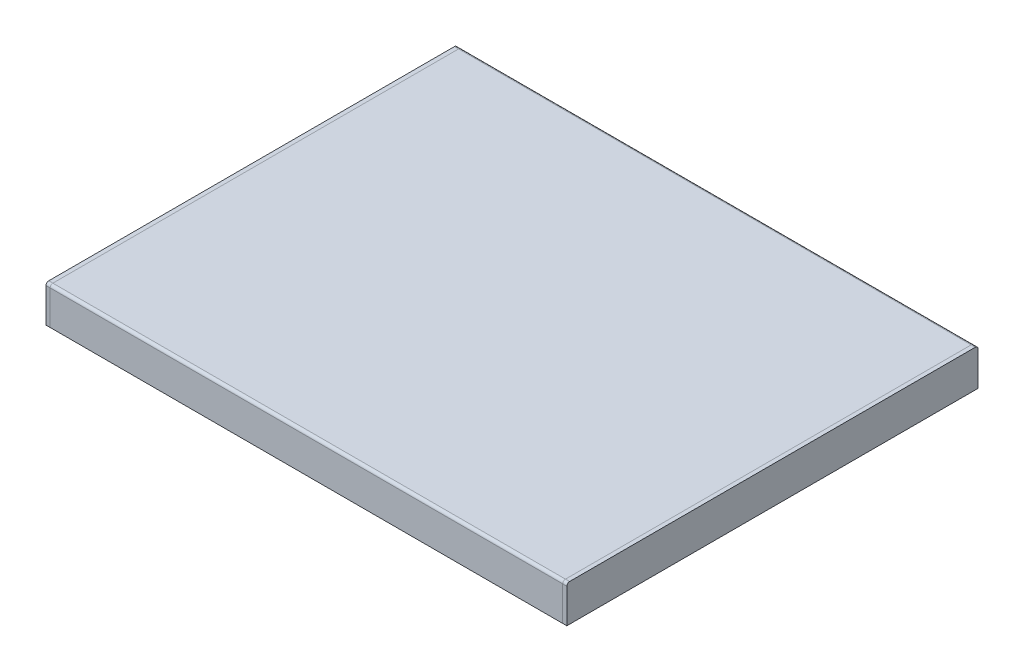
SolidWorks part; units mm, degrees
ref_plane "Front Plane" through (0, 0, 0) normal (0, 0, 1) x (1, 0, 0)
ref_plane "Top Plane" through (0, 0, 0) normal (0, 1, 0) x (1, 0, 0)
ref_plane "Right Plane" through (0, 0, 0) normal (1, 0, 0) x (0, 0, -1)
sketch "Sketch1" plane through (0, 0, 0) normal (0, 1, 0) x (1, 0, 0)
  line L1 (-187, -150) -> (187, -150)
  line L2 (-187, -150) -> (-187, 150)
  line L3 (-187, 150) -> (187, 150)
  line L4 (187, -150) -> (187, 150)
  line L5 (-187, -150) -> (187, 150) construction
  line L6 (-187, 150) -> (187, -150) construction
  point P0 (0, 0)
  dimension "D1" = 300
  dimension "D2" = 374
extrude "Body" add sketch "Sketch1" along normal blind 27
sketch "Sketch2" plane through (0, 0, 0) normal (0, -1, 0) x (1, 0, 0)
  line L2 (-187, -150) -> (-187, 150) construction
  line L3 (152, -115) -> (-152, -115) construction
  line L4 (152, -115) -> (152, 115) construction
  line L5 (152, 115) -> (-152, 115) construction
  line L6 (-152, -115) -> (-152, 115) construction
  line L7 (152, -115) -> (-152, 115) construction
  line L8 (152, 115) -> (-152, -115) construction
  line L9 (187, -150) -> (-187, -150) construction
  circle A0 centre (-152, 115) radius 20
  circle A1 centre (152, 115) radius 20
  circle A2 centre (-152, -115) radius 20
  circle A3 centre (152, -115) radius 20
  point P12 (0, 0)
  dimension "D1" = 40
  dimension "D2" = 35
  dimension "D3" = 35
extrude "Feet" add sketch "Sketch2" along normal blind 7 separate body
fillet "Edges" radius 2 2 edges at (0, 27, -150) (0, 27, 150)
sketch "Sketch4" plane through (-187, 0, 0) normal (-1, 0, 0) x (0, 0, 1)
  line L4 (148, 27) -> (-148, 27)
  line L5 (-150, 25) -> (-150, 0)
  line L6 (-150, 0) -> (150, 0)
  line L7 (150, 0) -> (150, 25)
  line L8 (148, 27) -> (-148, 27)
  line L9 (-150, 25) -> (-150, 0)
  line L10 (-150, 0) -> (150, 0)
  line L11 (150, 0) -> (150, 25)
  arc A2 (-148, 27) -> (-150, 25) centre (-148, 25) ccw
  arc A3 (150, 25) -> (148, 27) centre (148, 25) ccw
  arc A4 (-148, 27) -> (-150, 25) centre (-148, 25) ccw
  arc A5 (150, 25) -> (148, 27) centre (148, 25) ccw
  dimension "D1" = 0
extrude "End Cap A" add sketch "Sketch4" along normal blind 3 separate body
extrude "End Cap B" add sketch "Sketch4<2>" against normal blind 3 from surface separate body starting at face at (187, 17.4714, 0)
sketch "Sketch4<2>" plane through (-187, 0, 0) normal (-1, 0, 0) x (0, 0, 1) same geometry as "Sketch4"
sketch "Sketch5" plane through (0, -7, 0) normal (0, -1, 0) x (1, 0, 0)
  circle A0 centre (-152, 115) radius 16
  circle A1 centre (152, 115) radius 16
  circle A2 centre (152, -115) radius 16
  circle A3 centre (-152, -115) radius 16
  circle A4 centre (-152, -115) radius 20 construction
  dimension "D1" = 4
extrude "Boss-Extrude8" add sketch "Sketch5" along normal blind 5
move or copy body "Body-Move/Copy1" [suppressed] bodies to move or copy 101 107 108 109 110 111 112
